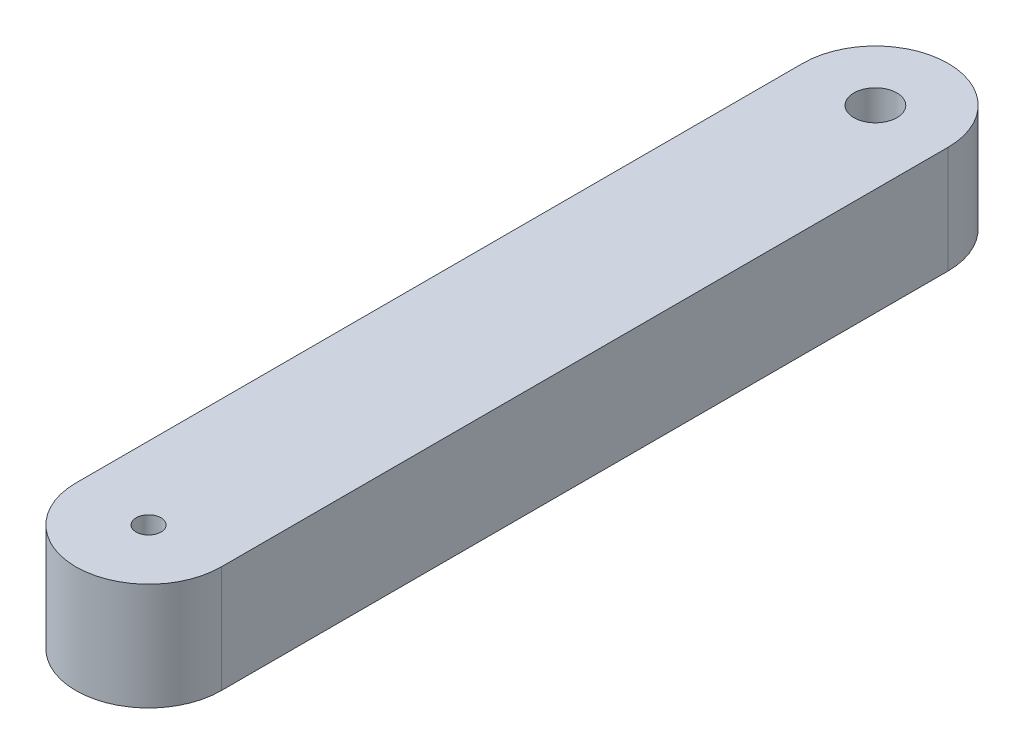
SolidWorks part; units mm, degrees
material "PLA Infill"
ref_plane "Front Plane" through (0, 0, 0) normal (0, 0, 1) x (1, 0, 0)
ref_plane "Top Plane" through (0, 0, 0) normal (0, 1, 0) x (1, 0, 0)
ref_plane "Right Plane" through (0, 0, 0) normal (1, 0, 0) x (0, 0, -1)
sketch "Sketch1" plane through (0, 0, 0) normal (0, 1, 0) x (1, 0, 0)
  line L0 (0, -60) -> (0, 60) construction
  line L1 (-12, -60) -> (-12, 60)
  line L2 (12, -60) -> (12, 60)
  arc A0 (-12, -60) -> (12, -60) centre (0, -60) ccw
  arc A1 (12, 60) -> (-12, 60) centre (0, 60) ccw
  circle A2 centre (0, 60) radius 2.05
  circle A3 centre (0, -60) radius 2.05
  point P2 (0, 0)
  dimension "D1" = 12
  dimension "D3" = 4.1
  dimension "D2" = 120
extrude "Boss-Extrude1" add sketch "Sketch1" along normal blind 17.7
sketch "Sketch2" plane through (0, 17.7, 0) normal (0, 1, 0) x (1, 0, 0)
  circle A0 centre (0, 60) radius 3.55
  dimension "D1" = 7.1
extrude "Cut-Extrude1" cut sketch "Sketch2" against normal blind 6
